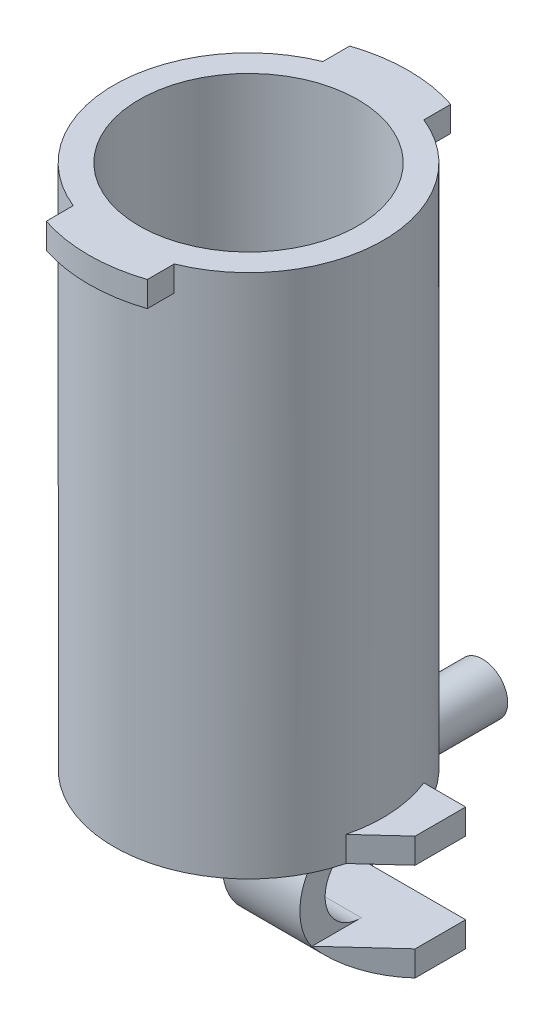
SolidWorks part; units mm, degrees
ref_plane "Front Plane" through (0, 0, 0) normal (0, 0, 1) x (1, 0, 0)
ref_plane "Top Plane" through (0, 0, 0) normal (0, 1, 0) x (1, 0, 0)
ref_plane "Right Plane" through (0, 0, 0) normal (1, 0, 0) x (0, 0, -1)
sketch "Sketch1" plane through (0, 0, 0) normal (0, 1, 0) x (1, 0, 0)
  circle A0 centre (0, 0) radius 8
extrude "Boss-Extrude1" add sketch "Sketch1" along normal blind 31.2
shell "Shell1" thickness 1.5 removed face at (0, 31.2, 8)
sketch "Sketch2" plane through (0, 0, 0) normal (0, -1, 0) x (1, 0, 0)
  circle A2 centre (0, -3) radius 3.5
extrude "Boss-Extrude2" add sketch "Sketch2" along normal blind 5.3
sketch "Sketch3" plane through (0, 0, 0) normal (1, 0, 0) x (0, 0, -1)
  line L0 (0, 4.9697) -> (0, 0) construction
  line L1 (0, 1.5) -> (0, 0)
  line L2 (0, -4.3) -> (0, -5.8)
  line L3 (0, -4.3) -> (0, -6.6365) construction
  arc A0 (0, 0) -> (0, -4.3) centre (0, -2.15) ccw
  arc A1 (0, 1.5) -> (0, -5.8) centre (0, -2.15) ccw
extrude "Boss-Extrude3" add sketch "Sketch3" along normal blind 6.7 contours A1 L2 A0 L1
sketch "Sketch4" plane through (0, -5.3, 0) normal (0, -1, 0) x (1, 0, 0)
  line L0 (0, 0) -> (2.1, 0)
  line L1 (6.7, 0) -> (0, 0) construction
  line L2 (2.1, 0) -> (2.1, 5.477)
  line L3 (2.1, 5.477) -> (0, 5.477)
  line L4 (0, 5.477) -> (0, 0)
extrude "Cut-Extrude1" cut sketch "Sketch4" along normal blind 9
sketch "Sketch5" plane through (0, 0, 0) normal (0, -1, 0) x (1, 0, 0)
  line L0 (0, 0.5) -> (0, 3.65)
  line L1 (0, 3.65) -> (0, 1.8439) construction
  line L2 (2.1, -0.2) -> (2.1, 3.65)
  line L3 (6.7, 3.65) -> (0, 3.65) construction
  line L4 (2.1, 3.65) -> (0, 3.65)
  arc A0 (2.1, -0.2) -> (0, 0.5) centre (0, -3) ccw
extrude "Cut-Extrude2" cut sketch "Sketch5" along normal blind 9
sketch "Sketch6" plane through (0, -5.3, 0) normal (0, -1, 0) x (1, 0, 0)
  line L0 (-1.4347, -3) -> (2.2984, -3) construction
ref_plane "Plane1" through (0, 0, -3) normal (0, 0, 1) x (1, 0, 0)
sketch "Sketch8" plane through (0, 0, -3) normal (0, 0, 1) x (1, 0, 0)
  line L0 (0, 0) -> (0, -7.6173) construction
  circle A1 centre (0, -2.7845) radius 2.45
extrude "Boss-Extrude4" add sketch "Sketch8" against normal blind 4.8
sketch "Sketch9" plane through (0, 0, -7.8) normal (0, 0, -1) x (-1, 0, 0)
  circle A0 centre (0, -2.7845) radius 1.5
extrude "Boss-Extrude5" add sketch "Sketch9" along normal blind 6.1
sketch "Sketch10" plane through (0, 0, -13.9) normal (0, 0, -1) x (-1, 0, 0)
  circle A0 centre (0, -2.7845) radius 0.75
extrude "Cut-Extrude3" cut sketch "Sketch10" against normal blind 10.1
sketch "Sketch11" plane through (0, -5.3, 0) normal (0, -1, 0) x (1, 0, 0)
  circle A1 centre (0, -3) radius 2
extrude "Cut-Extrude4" cut sketch "Sketch11" against normal through all
sketch "Sketch12" plane through (0, -5.3, 0) normal (0, -1, 0) x (1, 0, 0)
  circle A0 centre (0, -3) radius 2
extrude "Boss-Extrude6" add sketch "Sketch12" against normal blind 1.5 separate body
sketch "Sketch16" plane through (6.7, 0, 0) normal (1, 0, 0) x (0, 0, -1)
  line L0 (0, -4.3) -> (0, -5.8)
  line L1 (0, -4.3) -> (3, -4.3)
  line L2 (0, -5.8) -> (3, -5.8)
  line L3 (3, -4.3) -> (3, -5.8)
  line L4 (0, -4.3) -> (0, -5.8) construction
  line L5 (-2.15, -2.15) -> (-4.1057, -2.15) construction
  line L6 (0, 1.5) -> (3, 1.5)
  line L7 (3, 0) -> (3, 1.5)
  line L8 (0, 0) -> (3, 0)
  line L9 (0, 0) -> (0, 1.5)
  arc A0 (0, 0) -> (0, -4.3) centre (0, -2.15) ccw construction
extrude "Boss-Extrude9" add sketch "Sketch16" along normal blind 3.2 and the other way up to surface (4.6 mm away) other way up to face at (2.1, -2.7511, 1.7196)
sketch "Sketch17" plane through (0, -4.3, 0) normal (0, 1, 0) x (1, 0, 0)
  line L0 (6.7, 0) -> (6.7, -2.9284)
  line L5 (6.7, -2.9284) -> (9.9, 0)
  line L6 (9.9, 3) -> (9.9, 0) construction
  line L7 (9.9, 0) -> (6.7, 0)
extrude "Boss-Extrude10" add sketch "Sketch17" against normal up to surface (1.5 mm away) contours L0 L5 L7 up to face at (6.14, -5.8, -1.2)
sketch "Sketch18" plane through (6.7, 0, 0) normal (-1, 0, 0) x (0, 0, 1)
  line L0 (2.9284, -5.8) -> (2.9284, -4.3288)
  line L1 (2.9284, -5.8) -> (0, -5.8)
  arc A0 (0, -5.8) -> (2.9284, -4.3288) centre (0, -2.15) ccw
extrude "Cut-Extrude5" cut sketch "Sketch18" against normal through all
sketch "Sketch19" plane through (0, -4.3, 0) normal (0, 1, 0) x (1, 0, 0)
  line L0 (9.9, 0) -> (6.7, -2.9284)
  line L5 (6.7, 0) -> (6.7, -2.9284)
  line L6 (9.9, 0) -> (6.7, 0)
extrude "Boss-Extrude11" add sketch "Sketch19" along normal up to surface (5.8 mm away) contours L0 L5 L6 up to face at (8.8402, 1.5, -1.507)
sketch "Sketch20" plane through (0, 0, 0) normal (0, 0, -1) x (-1, 0, 0)
  line L0 (-3.5, -4.3) -> (-9.9, -4.3) construction
  line L1 (-9.9, 0) -> (-6.7, 0)
  line L2 (-9.9, 0) -> (-9.9, -4.3)
  line L3 (-9.9, -4.3) -> (-6.7, -4.3)
  line L4 (-6.7, 0) -> (-6.7, -4.3)
extrude "Cut-Extrude6" cut sketch "Sketch20" against normal through all
sketch "Sketch21" plane through (2.1, 0, 0) normal (-1, 0, 0) x (0, 0, 1)
  circle A0 centre (0, -2.15) radius 2.15
extrude "Boss-Extrude12" add sketch "Sketch21" against normal blind 0.001
mirror "Mirror1" about plane through (0, 0, 0) normal (1, 0, 0) of bodies 119
sketch "Sketch22" plane through (0, 31.2, 0) normal (0, 1, 0) x (1, 0, 0)
  line L2 (3, 7.4162) -> (3, 9.0139)
  line L4 (-3, 7.4162) -> (-3, 9.0139)
  line L5 (3, -7.4162) -> (3, -9.0139)
  line L6 (-3, -7.4162) -> (-3, -9.0139)
  arc A0 (3, 9.0139) -> (-3, 9.0139) centre (0, 0) ccw
  arc A1 (3, 7.4162) -> (-3, 7.4162) centre (0, 0) ccw
  arc A2 (3, -7.4162) -> (-3, -7.4162) centre (0, 0) cw
  arc A3 (3, -9.0139) -> (-3, -9.0139) centre (0, 0) cw
extrude "Boss-Extrude13" add sketch "Sketch22" against normal blind 1.5
